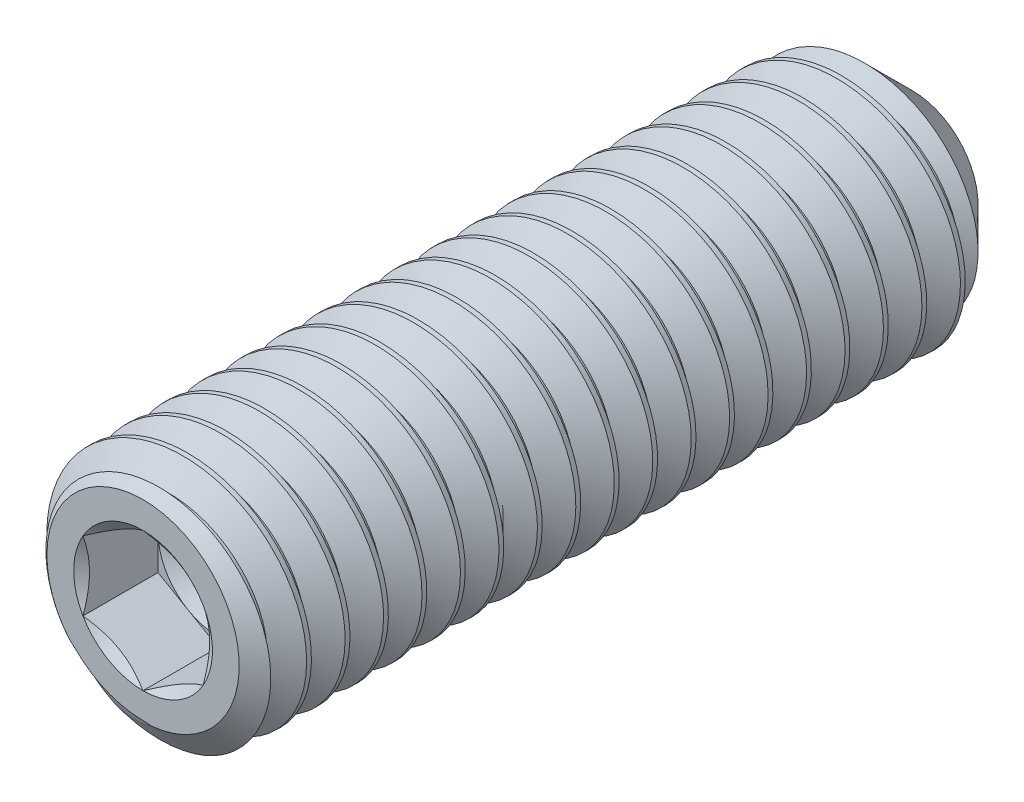
SolidWorks part; units mm, degrees
ref_plane "Front" through (0, 0, 0) normal (0, 0, 1) x (1, 0, 0)
ref_plane "Top" through (0, 0, 0) normal (0, 1, 0) x (1, 0, 0)
ref_plane "Right" through (0, 0, 0) normal (1, 0, 0) x (0, 0, -1)
sketch "Body Sketch" plane through (0, 0, 0) normal (1, 0, 0) x (0, 0, -1)
  line L0 (-7.5884, 0) -> (-7.5884, 2)
  line L1 (-7.5884, 2) -> (-7.2383, 2.5)
  line L2 (-7.2383, 2.5) -> (7.2815, 2.5)
  line L3 (7.2815, 2.5) -> (8.4116, 1.3699)
  line L4 (0.0216, 2.5) -> (0.0216, -2.5) construction
  line L5 (7.5884, 0) -> (-7.5884, 0)
  line L6 (-7.5884, 2) -> (-7.5884, -2) construction
  line L7 (7.5884, 0) -> (8.4116, 1.3699)
  line L8 (7.5884, 0) -> (8.4116, -1.3699) construction
  line L10 (7.5884, 0) -> (8.4116, 0) construction
  line L11 (8.4116, 1.3699) -> (8.4116, 0) construction
  point P11 (0.0216, 0)
  dimension "Length" = 16
  dimension "Top Chamfer" = 35
  dimension "Diameter" = 5
  dimension "D1" = 4
  dimension "D2" = 118
  dimension "D3" = 45
revolve "Body Revolve" add sketch "Body Sketch" angle 360 about L5
ref_plane "Bottom of Tip Plane" through (0, 0, -8.4116) normal (0, 0, 1) x (1, 0, 0)
sketch "Spiral Sketch" plane through (0, 0, -8.4116) normal (0, 0, 1) x (1, 0, 0)
  circle A0 centre (0, 0) radius 2.5 construction
  circle A1 centre (0, 0) radius 2.5
curve "Helix/Spiral" pitch 0.8 height 16.8 radius 2.5 centre (0, 0, -8.4116) axis (0, 0, 1) start towards (0, 1, 0) parameters "Thread Pitch"=0.8
sketch "Cut Sweep Sketch" plane through (0, 0, 0) normal (1, 0, 0) x (0, 0, -1)
  line L0 (8.4116, 2.5) -> (9.1116, 2.5)
  line L1 (9.1116, 2.5) -> (8.8116, 1.9804)
  line L2 (8.8116, 1.9804) -> (8.7116, 1.9804)
  line L3 (8.7116, 1.9804) -> (8.4116, 2.5)
  line L4 (8.5616, 2.2402) -> (8.9616, 2.2402) construction
  line L6 (-7.2383, 2.5) -> (7.2815, 2.5) construction
  dimension "D1" = 0.1
  dimension "D3" = 60
  dimension "D2" = 0.4
sweep "Cut Sweep" cut profiles "Cut Sweep Sketch" path "Helix/Spiral" align with end faces yes
sketch "Hex Sketch" plane through (0, 0, 7.5884) normal (0, 0, 1) x (1, 0, 0)
  line L1 (0, 1.4434) -> (-1.25, 0.7217)
  line L2 (-1.25, 0.7217) -> (-1.25, -0.7217)
  line L3 (-1.25, -0.7217) -> (0, -1.4434)
  line L4 (0, -1.4434) -> (1.25, -0.7217)
  line L5 (1.25, -0.7217) -> (1.25, 0.7217)
  line L6 (1.25, 0.7217) -> (0, 1.4434)
  circle A0 centre (0, 0) radius 1.25 construction
  dimension "Hex" = 2.5
extrude "Hex Extrude" cut sketch "Hex Sketch" against normal blind 1.5625
sketch "Hex Entry Sketch" plane through (0, 0, 7.5884) normal (0, 0, 1) x (1, 0, 0)
  circle A0 centre (0, 0) radius 1.4434
extrude "Hex Entry Extrude" cut sketch "Hex Entry Sketch" against normal through all draft 55
sketch "Hex Bottom Sketch" plane through (0, 0, 6.0259) normal (0, 0, 1) x (1, 0, 0)
  circle A0 centre (0, 0) radius 1.25 construction
  circle A1 centre (0, 0) radius 1.25
extrude "Hex Bottom Extrude" cut sketch "Hex Bottom Sketch" against normal through all draft 60
equation "\"D1@Cut Sweep Sketch\" = \"Thread Pitch@Helix/Spiral\" * .125"
equation "\"D2@Cut Sweep Sketch\" = \"Thread Pitch@Helix/Spiral\" * .5"
equation "\"D3@Helix/Spiral\" = \"Length@Body Sketch\" + \"Thread Pitch@Helix/Spiral\""
equation "\"hex Depth@Hex Extrude\" = \"Hex@Hex Sketch\" * .625"
equation "\"D1@Body Sketch\" = \"Diameter@Body Sketch\" * .8"
equation "\"Diameter\"= 5mm"
equation "\"Thread Pitch\"= 0.8mm"
equation "\"Hex Size\"= 2.5mm"
equation "\"Diameter@Body Sketch\"=\"Diameter\""
equation "\"Thread Pitch@Helix/Spiral\"=\"Thread Pitch\""
equation "\"Hex@Hex Sketch\"=\"Hex Size\""
